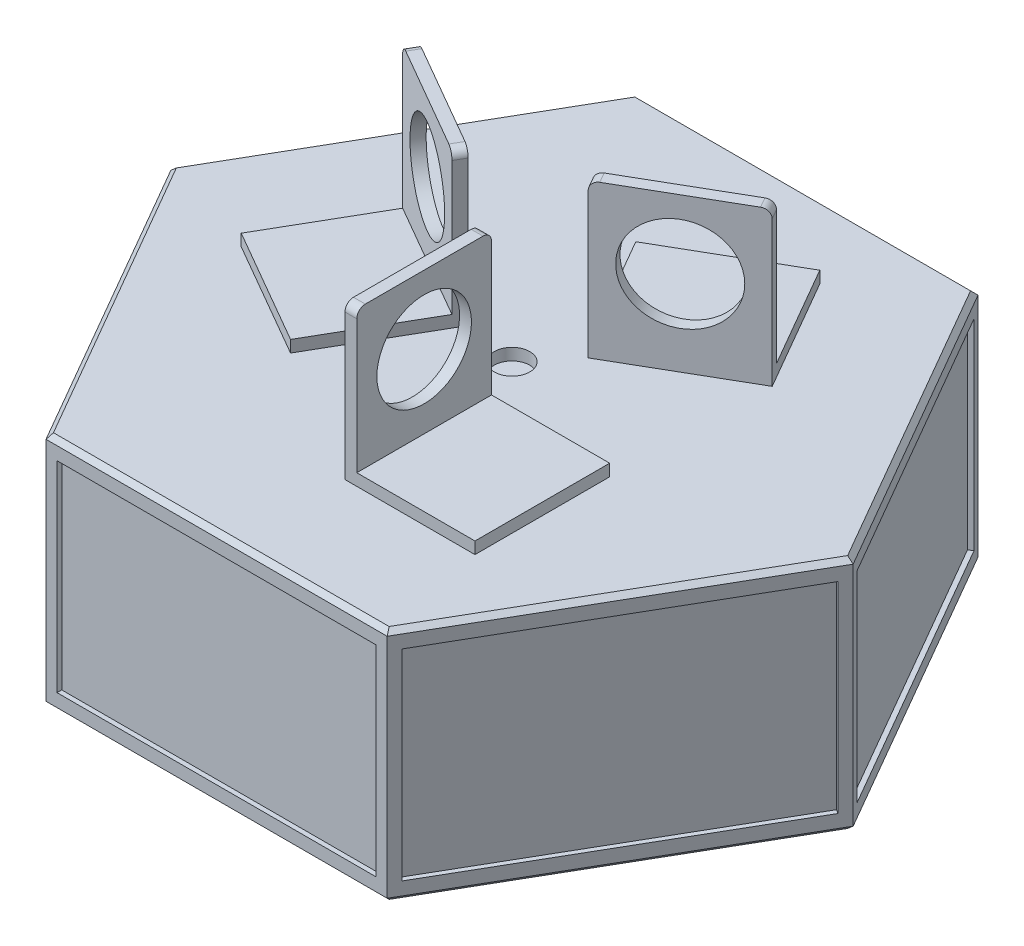
SolidWorks part; units mm, degrees
ref_plane "Front Plane" through (0, 0, 0) normal (0, 0, 1) x (1, 0, 0)
ref_plane "Top Plane" through (0, 0, 0) normal (0, 1, 0) x (1, 0, 0)
ref_plane "Right Plane" through (0, 0, 0) normal (1, 0, 0) x (0, 0, -1)
sketch "Sketch1" plane through (0, 0, 0) normal (0, 1, 0) x (1, 0, 0)
  line L1 (72.1688, 125) -> (-72.1688, 125)
  line L2 (-72.1688, 125) -> (-144.3376, 0)
  line L3 (-144.3376, 0) -> (-72.1688, -125)
  line L4 (-72.1688, -125) -> (72.1688, -125)
  line L5 (72.1688, -125) -> (144.3376, 0)
  line L6 (144.3376, 0) -> (72.1688, 125)
  circle A0 centre (0, 0) radius 125 construction
  dimension "D1" = 250
extrude "Boss-Extrude1" add sketch "Sketch1" along normal blind 100
sketch "Sketch2" plane through (0, 100, 0) normal (0, 1, 0) x (1, 0, 0)
  line L0 (0, 0) -> (0, -125) construction
  line L1 (-72.1688, -125) -> (72.1688, -125) construction
  line L2 (0, -50) -> (7.8312, -50) construction
  line L4 (12.8312, -78.5) -> (7.8312, -78.5)
  line L5 (12.8312, -78.5) -> (12.8312, -21.5)
  line L6 (12.8312, -21.5) -> (7.8312, -21.5)
  line L7 (7.8312, -78.5) -> (7.8312, -21.5)
  line L8 (12.8312, -78.5) -> (7.8312, -21.5) construction
  line L9 (12.8312, -21.5) -> (7.8312, -78.5) construction
  point P7 (10.3312, -50)
  point P22 (0, 0)
  dimension "D1" = 5
  dimension "D2" = 57
  dimension "D3" = 50
  dimension "D4" = 80
extrude "Boss-Extrude2" add sketch "Sketch2" along normal blind 65
sketch "Sketch3" plane through (7.8312, 0, 0) normal (-1, 0, 0) x (0, 0, 1)
  line L0 (0, 100) -> (125, 100) construction
  line L1 (50, 136) -> (50, 100) construction
  line L2 (78.5, 100) -> (21.5, 100) construction
  circle A0 centre (50, 136) radius 20
  dimension "D1" = 40
  dimension "D2" = 36
extrude "Cut-Extrude1" cut sketch "Sketch3" against normal through all
sketch "Sketch7" plane through (12.8312, 0, 0) normal (1, 0, 0) x (0, 0, -1)
  line L0 (-50, 100) -> (-50, 105) construction
  line L1 (-78.5, 100) -> (-21.5, 100) construction
  line L2 (-21.5, 165) -> (-21.5, 100) construction
  line L3 (-78.5, 100) -> (-21.5, 100)
  line L4 (-78.5, 100) -> (-78.5, 105)
  line L5 (-78.5, 105) -> (-21.5, 105)
  line L6 (-21.5, 100) -> (-21.5, 105)
  line L7 (-78.5, 100) -> (-21.5, 105) construction
  line L8 (-78.5, 105) -> (-21.5, 100) construction
  point P4 (-50, 102.5)
  dimension "D1" = 5
extrude "Boss-Extrude3" add sketch "Sketch7" along normal blind 50
fillet "Fillet1" radius 3.6 2 edges at (10.3312, 165, 21.5) (10.3312, 165, 78.5)
sketch "Sketch6" plane through (0, 0, 125) normal (0, 0, 1) x (1, 0, 0)
  line L0 (0, 0) -> (0, 100) construction
  line L1 (-72.1688, 0) -> (72.1688, 0) construction
  line L2 (-72.1688, 100) -> (72.1688, 100) construction
  line L4 (-67.5, 7.5) -> (67.5, 7.5)
  line L5 (-67.5, 7.5) -> (-67.5, 92.5)
  line L6 (-67.5, 92.5) -> (67.5, 92.5)
  line L7 (67.5, 7.5) -> (67.5, 92.5)
  line L8 (-67.5, 7.5) -> (67.5, 92.5) construction
  line L9 (-67.5, 92.5) -> (67.5, 7.5) construction
  point P6 (0, 50)
  dimension "D1" = 85
  dimension "D2" = 135
extrude "Cut-Extrude2" cut sketch "Sketch6" against normal blind 2
ref_axis "Axis1" through (0, 0, 0) along (0, 1, 0)
pattern_circular "CirPattern1" count 3 over 360 about axis through (0, 0, 0) along (0, 1, 0) of "Boss-Extrude2", "Cut-Extrude1", "Boss-Extrude3", "Fillet1"
pattern_circular "CirPattern2" count 6 over 360 about axis through (0, 0, 0) along (0, 1, 0) of "Cut-Extrude2"
chamfer "Chamfer1" distance 2 angle 45 12 edges at (108.2532, 0, -62.5) (0, 0, -125) (-108.2532, 0, -62.5) (-108.2532, 0, 62.5) (108.2532, 0, 62.5) (0, 0, 125) (-108.2532, 100, 62.5) (-108.2532, 100, -62.5) (0, 100, -125) (108.2532, 100, -62.5) (108.2532, 100, 62.5) (0, 100, 125)
sketch "Sketch8" plane through (0, 100, 0) normal (0, 1, 0) x (1, 0, 0)
  circle A0 centre (0, 0) radius 7.5
  dimension "D1" = 15
extrude "Cut-Extrude3" cut sketch "Sketch8" against normal blind 5
